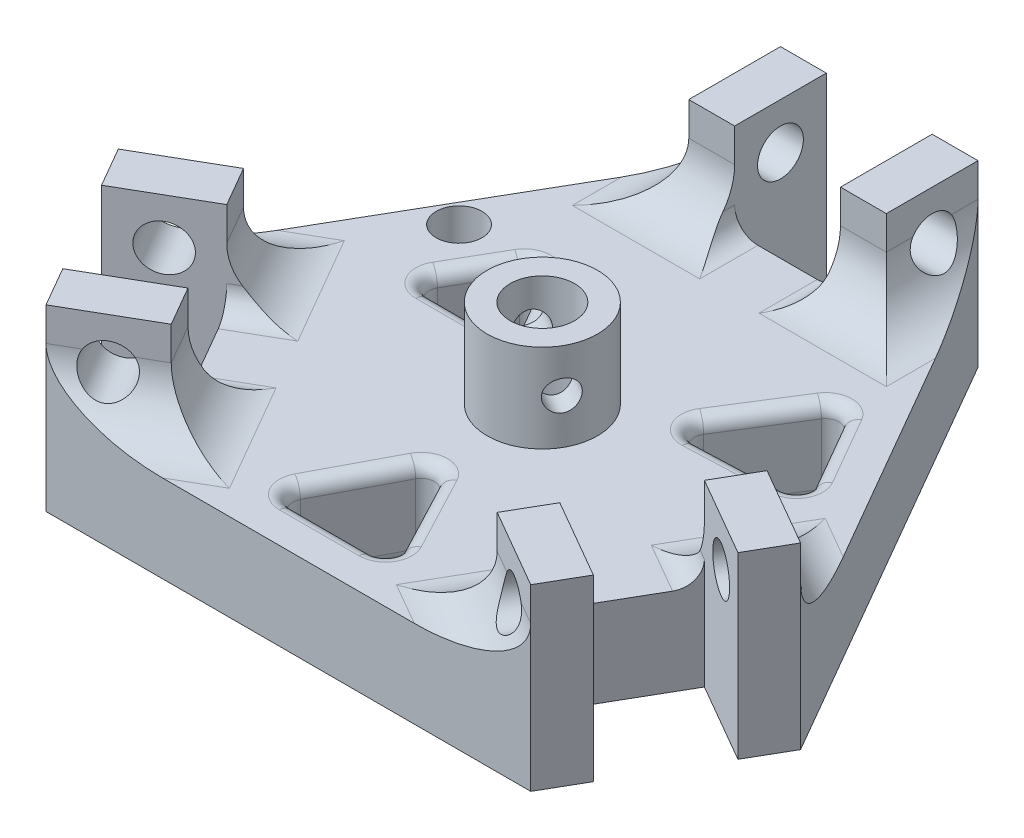
SolidWorks part; units mm, degrees
ref_plane "Front Plane" through (0, 0, 0) normal (0, 0, 1) x (1, 0, 0)
ref_plane "Top Plane" through (0, 0, 0) normal (0, 1, 0) x (1, 0, 0)
ref_plane "Right Plane" through (0, 0, 0) normal (1, 0, 0) x (0, 0, -1)
sketch "Sketch1" plane through (0, 0, 0) normal (0, 1, 0) x (1, 0, 0)
  line L0 (-51.3264, 0) -> (-41.3264, -17.3205)
  line L1 (-41.3264, -17.3205) -> (41.3264, -17.3205)
  line L2 (41.3264, -17.3205) -> (51.3264, 0)
  line L3 (51.3264, 0) -> (10, 71.5795)
  line L4 (10, 71.5795) -> (-10, 71.5795)
  line L5 (-10, 71.5795) -> (-51.3264, 0)
  line L6 (-51.3264, 0) -> (51.3264, 0) construction
  line L13 (-74.4204, 0) -> (-52.8734, -37.3205)
  line L14 (-52.8734, -37.3205) -> (52.8734, -37.3205)
  line L15 (52.8734, -37.3205) -> (74.4204, 0)
  line L16 (74.4204, 0) -> (21.547, 91.5795)
  line L17 (21.547, 91.5795) -> (-21.547, 91.5795)
  line L18 (-21.547, 91.5795) -> (-74.4204, 0)
  dimension "D1" = 20
  dimension "D2" = 88.9
  dimension "D3" = 20
extrude "Boss-Extrude1" add sketch "Sketch1" along normal blind 19.05 contours L13 L14 L15 L16 L17 L18
sketch "Sketch2" plane through (0, 19.05, 0) normal (0, 1, 0) x (1, 0, 0)
  line L0 (52.0999, 1.3397) -> (57.0999, 10)
  line L1 (21.547, 71.5795) -> (11.547, 71.5795)
  line L2 (21.547, 71.5795) -> (21.547, 91.5795)
  line L3 (21.547, 91.5795) -> (11.547, 91.5795)
  line L4 (11.547, 71.5795) -> (11.547, 91.5795)
  line L5 (-11.547, 71.5795) -> (-21.547, 71.5795)
  line L6 (-11.547, 71.5795) -> (-11.547, 91.5795)
  line L7 (-11.547, 91.5795) -> (-21.547, 91.5795)
  line L8 (-21.547, 71.5795) -> (-21.547, 91.5795)
  line L9 (52.0999, 1.3397) -> (69.4204, -8.6603)
  line L10 (57.0999, 10) -> (74.4204, 0)
  line L11 (69.4204, -8.6603) -> (74.4204, 0)
  line L12 (52.0999, 1.3397) -> (74.4204, 0) construction
  line L13 (57.0999, 10) -> (69.4204, -8.6603) construction
  line L14 (52.8734, -37.3205) -> (35.5529, -27.3205)
  line L15 (52.8734, -37.3205) -> (57.8734, -28.6603)
  line L16 (35.5529, -27.3205) -> (40.5529, -18.6603)
  line L17 (57.8734, -28.6603) -> (40.5529, -18.6603)
  line L18 (52.8734, -37.3205) -> (40.5529, -18.6603) construction
  line L19 (35.5529, -27.3205) -> (57.8734, -28.6603) construction
  line L20 (-52.8734, -37.3205) -> (-57.8734, -28.6603)
  line L21 (-52.8734, -37.3205) -> (-35.5529, -27.3205)
  line L22 (-57.8734, -28.6603) -> (-40.5529, -18.6603)
  line L23 (-35.5529, -27.3205) -> (-40.5529, -18.6603)
  line L24 (-52.8734, -37.3205) -> (-40.5529, -18.6603) construction
  line L25 (-57.8734, -28.6603) -> (-35.5529, -27.3205) construction
  line L26 (-69.4204, -8.6603) -> (-74.4204, 0)
  line L27 (-69.4204, -8.6603) -> (-52.0999, 1.3397)
  line L28 (-74.4204, 0) -> (-57.0999, 10)
  line L29 (-52.0999, 1.3397) -> (-57.0999, 10)
  line L30 (-69.4204, -8.6603) -> (-57.0999, 10) construction
  line L31 (-74.4204, 0) -> (-52.0999, 1.3397) construction
  point P8 (0, 0)
  point P9 (63.2602, 0.6699)
  point P10 (46.7132, -27.9904)
  point P11 (-46.7132, -27.9904)
  point P16 (-63.2602, 0.6699)
  point P21 (0, 0)
  point P26 (0, 0)
  point P31 (-38.2137, -16.6689)
  point P32 (0, 0)
  point P33 (0, 0)
  point P35 (0, 0)
  point P37 (0, 0)
  point P39 (0, 0)
  point P41 (0, 0)
  point P42 (0, 0)
  point P43 (0, 0)
  point P51 (0, 0)
  point P52 (0, 0)
  point P54 (0, 0)
  point P55 (0, 0)
  dimension "D1" = 20
  dimension "D2" = 10
extrude "Boss-Extrude2" add sketch "Sketch2" along normal blind 20
sketch "Sketch3" plane through (-21.547, 0, 0) normal (-1, 0, 0) x (0, 0, 1)
  line L0 (-91.5795, 39.05) -> (-71.5795, 39.05) construction
  line L1 (-71.5795, 39.05) -> (-71.5795, 19.05) construction
  circle A0 centre (-81.5795, 29.05) radius 5
  dimension "D1" = 10
  dimension "D2" = 10
  dimension "D3" = 10
extrude "Cut-Extrude1" cut sketch "Sketch3" against normal through all
sketch "Sketch4" plane through (-18.6051, 0, -32.225) normal (-0.5, 0, -0.866) x (-0.866, 0, 0.5)
  line L0 (44.45, 39.05) -> (44.45, 19.05) construction
  line L1 (44.45, 39.05) -> (64.45, 39.05) construction
  circle A0 centre (54.45, 29.05) radius 5
  dimension "D1" = 10
  dimension "D2" = 10
  dimension "D3" = 10
extrude "Cut-Extrude2" cut sketch "Sketch4" against normal through all
sketch "Sketch5" plane through (-2.9419, 0, 5.0955) normal (-0.5, 0, 0.866) x (0.866, 0, 0.5)
  line L0 (44.45, 39.05) -> (64.45, 39.05) construction
  line L1 (44.45, 39.05) -> (44.45, 19.05) construction
  circle A0 centre (54.45, 29.05) radius 5
  dimension "D1" = 10
  dimension "D2" = 10
  dimension "D3" = 10
extrude "Cut-Extrude3" cut sketch "Sketch5" against normal through all
sketch "Sketch6" plane through (0, 19.05, 0) normal (0, 1, 0) x (1, 0, 0)
  line L0 (-69.4204, -8.6603) -> (-52.0999, 1.3397)
  line L1 (-52.0999, 1.3397) -> (-40.5529, -18.6603)
  line L2 (-40.5529, -18.6603) -> (-57.8734, -28.6603)
  line L3 (-57.8734, -28.6603) -> (-69.4204, -8.6603)
  line L4 (-11.547, 71.5795) -> (11.547, 71.5795)
  line L5 (11.547, 71.5795) -> (11.547, 91.5795)
  line L6 (11.547, 91.5795) -> (-11.547, 91.5795)
  line L7 (-11.547, 91.5795) -> (-11.547, 71.5795)
  line L8 (52.0999, 1.3397) -> (69.4204, -8.6603)
  line L9 (69.4204, -8.6603) -> (57.8734, -28.6603)
  line L10 (57.8734, -28.6603) -> (40.5529, -18.6603)
  line L11 (40.5529, -18.6603) -> (52.0999, 1.3397)
extrude "Cut-Extrude4" cut sketch "Sketch6" against normal through all
fillet "Fillet1" radius 12.7 12 edges at (38.0529, 19.05, 22.9904) (54.5999, 19.05, -5.6699) (16.547, 19.05, -71.5795) (-16.547, 19.05, -71.5795) (-38.0529, 19.05, 22.9904) (-54.5999, 19.05, -5.6699) (65.7602, 19.05, -5) (-65.7602, 19.05, -5) (-21.547, 19.05, -81.5795) (-44.2132, 19.05, 32.3205) (44.2132, 19.05, 32.3205) (21.547, 19.05, -81.5795)
fillet "Fillet2" radius 5.08 6 edges at (-11.547, 19.05, -65.2295) (11.547, 19.05, -65.2295) (-46.6007, 19.05, -4.5147) (-35.0537, 19.05, 15.4853) (46.6007, 19.05, -4.5147) (35.0537, 19.05, 15.4853)
scale "Scale1" scale about centroid uniform scaling yes scale factor 0.66
sketch "Sketch7" plane through (0, 16.4113, 0) normal (0, 1, 0) x (1, 0, 0)
  line L0 (0, 18.0863) -> (30.5755, 0.4336) construction
  line L1 (32.7096, 4.13) -> (28.4413, -3.2628) construction
  line L2 (0, 18.0863) -> (-30.5754, 0.4336) construction
  line L3 (-28.4413, -3.2628) -> (-32.7096, 4.13) construction
  line L4 (0, 18.0863) -> (0, 32.2583) construction
  line L7 (-4.2682, 53.3918) -> (4.2682, 53.3918) construction
  circle A0 centre (0, 18.0863) radius 4.6355
  dimension "D1" = 9.271
extrude "Cut-Extrude5" cut sketch "Sketch7" against normal through all
sketch "Sketch8" plane through (0, 16.4113, 0) normal (0, 1, 0) x (1, 0, 0)
  circle A0 centre (0, 18.0863) radius 4.6355
  circle A1 centre (0, 18.0863) radius 7.9497
extrude "Boss-Extrude3" add sketch "Sketch8" along normal blind 12.7
sketch "Sketch9" plane through (22.7438, 0, 13.1312) normal (0.866, 0, 0.5) x (0.5, 0, -0.866)
  line L0 (23.2842, 3.8383) -> (8.0422, 3.8383) construction
  circle A0 centre (15.6632, 22.8883) radius 2.159
  point P2 (0, 0)
  point P5 (15.6632, 3.8383)
  dimension "D2" = 4.318
  dimension "D1" = 19.05
extrude "Cut-Extrude6" cut sketch "Sketch9" against normal through all
sketch "Sketch10" plane through (0, 16.4113, 0) normal (0, 1, 0) x (1, 0, 0)
  line L0 (-22.603, 52.0738) -> (-40.7355, 20.6674) construction
  line L1 (-28.3697, 34.4656) -> (-31.6693, 36.3706) construction
  circle A0 centre (-28.3697, 34.4656) radius 3.302
  point P4 (0, 0)
  point P5 (-27.6363, 34.0421)
  dimension "D1" = 6.604
  dimension "D2" = 3.81
extrude "Cut-Extrude8" cut sketch "Sketch10" against normal through all
sketch "Sketch11" plane through (0, 16.4113, 0) normal (0, 1, 0) x (1, 0, 0)
  line L0 (21.725, 40.8945) -> (30.615, 25.4966)
  line L1 (30.615, 25.4966) -> (11.565, 24.7634)
  line L2 (11.565, 24.7634) -> (21.725, 40.8945)
  line L3 (0, 4.7322) -> (8.89, -12.1322)
  line L4 (8.89, -12.1322) -> (-8.89, -12.1322)
  line L5 (-8.89, -12.1322) -> (0, 4.7322)
  line L6 (-17.9606, 37.2547) -> (-25.5806, 24.0565)
  line L7 (-25.5806, 24.0565) -> (-10.3406, 24.0565)
  line L8 (-10.3406, 24.0565) -> (-17.9606, 37.2547)
  line L9 (40.7355, 20.6674) -> (22.603, 52.0738) construction
  line L10 (-18.1325, -18.4822) -> (18.1325, -18.4822) construction
  line L11 (26.17, 33.1956) -> (31.6693, 36.3706) construction
  line L12 (0, -12.1322) -> (0, -18.4822) construction
  line L15 (-22.603, 52.0738) -> (-40.7355, 20.6674) construction
  line L16 (-21.7706, 30.6556) -> (-31.6693, 36.3706) construction
  point P19 (0, -18.4822)
  dimension "D1" = 17.78
  dimension "D2" = 6.35
  dimension "D3" = 19.05
  dimension "D4" = 11.43
  dimension "D5" = 15.24
extrude "Cut-Extrude9" cut sketch "Sketch11" against normal through all
fillet "Fillet3" radius 1.905 27 edges at (-17.9606, 3.8383, -24.0565) (-17.9606, 16.4113, -24.0565) (-21.7706, 3.8383, -30.6556) (-21.7706, 16.4113, -30.6556) (0, 3.8383, 12.1322) (0, 16.4113, 12.1322) (-4.445, 3.8383, 3.7) (-4.445, 16.4113, 3.7) (16.645, 3.8383, -32.829) (16.645, 16.4113, -32.829) (26.17, 3.8383, -33.1956) (26.17, 16.4113, -33.1956) (-10.3406, 10.1248, -24.0565) (-14.1506, 3.8383, -30.6556) (-17.9606, 10.1248, -37.2547) (-14.1506, 16.4113, -30.6556) (8.89, 10.1248, 12.1322) (4.445, 3.8383, 3.7) (0, 10.1248, -4.7322) (4.445, 16.4113, 3.7) (11.565, 10.1248, -24.7634) (21.09, 3.8383, -25.13) (30.615, 10.1248, -25.4966) (21.09, 16.4113, -25.13) (-25.5806, 10.1248, -24.0565) (-8.89, 10.1248, 12.1322) (21.725, 10.1248, -40.8945)
